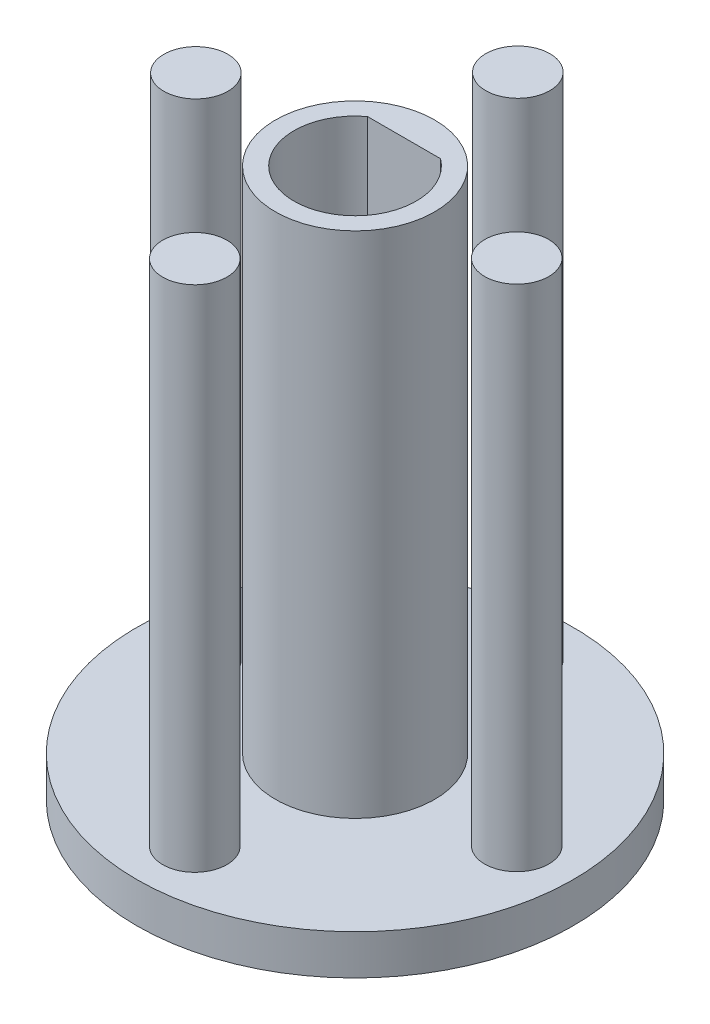
SolidWorks part; units mm, degrees
ref_plane "Front Plane" through (0, 0, 0) normal (0, 0, 1) x (1, 0, 0)
ref_plane "Top Plane" through (0, 0, 0) normal (0, 1, 0) x (1, 0, 0)
ref_plane "Right Plane" through (0, 0, 0) normal (1, 0, 0) x (0, 0, -1)
sketch "Sketch3" plane through (0, 0, 0) normal (0, 1, 0) x (1, 0, 0)
  line L0 (-7.9995, 0.0532) -> (0.009, 8.1156) construction
  line L1 (0.009, 8.1156) -> (8.0177, 0.0533) construction
  line L2 (8.0177, 0.0533) -> (0.0092, -8.0091) construction
  line L3 (0.0092, -8.0091) -> (-7.9995, 0.0532) construction
  line L7 (18.7783, 0.0532) -> (-25.5315, 0.0532) construction
  line L8 (9.7482, 0.0532) -> (10.8982, 0.0532)
  line L9 (-1.8231, 2.4452) -> (1.8231, 2.4452)
  line L11 (0.009, -13.1564) -> (0.009, 16.0208) construction
  circle A0 centre (0, 0) radius 10.9
  circle A1 centre (0.009, 8.1156) radius 1.6
  circle A2 centre (8.0177, 0.0533) radius 1.6
  circle A3 centre (0.0092, -8.0091) radius 1.6
  circle A4 centre (-7.9995, 0.0532) radius 1.6
  circle A5 centre (0, 0) radius 3.975
  arc A6 (-1.8231, 2.4452) -> (1.8231, 2.4452) centre (0, 0) ccw
  dimension "D1" = 21.8
extrude "Boss-Extrude1" add sketch "Sketch3" along normal blind 27.4 contours A4 | A3 | A2 | A1 | A6 L9 | A5
extrude "Boss-Extrude2" add sketch "Sketch3<17>" along normal blind 2 contours A0
sketch "Sketch3<17>" plane through (0, 0, 0) normal (0, 1, 0) x (1, 0, 0) same geometry as "Sketch3"
ref_plane "Plane1" through (1.8231, 27.4, -2.4452) normal (-0.8017, 0, -0.5977) x (-0.5977, 0, 0.8017)
